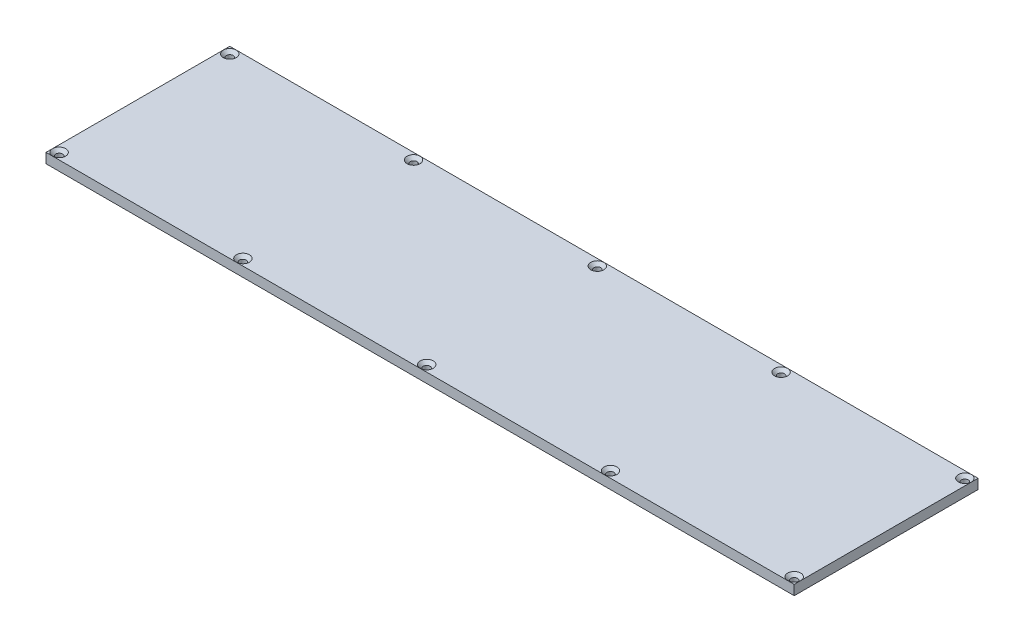
SolidWorks part; units mm, degrees
material "Wood floor laminate, Egger MED"
ref_plane "Front Plane" through (0, 0, 0) normal (0, 0, 1) x (1, 0, 0)
ref_plane "Top Plane" through (0, 0, 0) normal (0, 1, 0) x (1, 0, 0)
ref_plane "Right Plane" through (0, 0, 0) normal (1, 0, 0) x (0, 0, -1)
sketch "Sketch1" plane through (0, 0, 0) normal (0, 1, 0) x (1, 0, 0)
  line L1 (-361.95, -88.9) -> (361.95, -88.9)
  line L2 (-361.95, -88.9) -> (-361.95, 88.9)
  line L3 (-361.95, 88.9) -> (361.95, 88.9)
  line L4 (361.95, -88.9) -> (361.95, 88.9)
  line L5 (0, 88.9) -> (0, -88.9) construction
  line L6 (-361.95, 0) -> (361.95, 0) construction
  point P0 (0, 0)
  dimension "D1" = 723.9
  dimension "D2" = 177.8
extrude "Boss-Extrude1" add sketch "Sketch1" along normal blind 9.525
sketch "Sketch2" plane through (0, 9.525, 0) normal (0, 1, 0) x (1, 0, 0)
  line L0 (-361.95, -88.9) -> (361.95, -88.9) construction
  line L1 (-361.95, -88.9) -> (361.95, -88.9) construction
  line L2 (-361.95, -88.9) -> (-361.95, 88.9) construction
  line L3 (-361.95, 88.9) -> (361.95, 88.9) construction
  line L4 (361.95, -88.9) -> (361.95, 88.9) construction
  line L5 (0, 88.9) -> (0, -88.9) construction
  line L6 (-361.95, 0) -> (361.95, 0) construction
  line L7 (361.95, -88.9) -> (361.95, 88.9) construction
  line L8 (361.95, 88.9) -> (-361.95, 88.9) construction
  line L9 (-361.95, 88.9) -> (-361.95, -88.9) construction
  line L10 (-355.6, 82.55) -> (355.6, 82.55) construction
  line L11 (355.6, -82.55) -> (355.6, 82.55) construction
  line L12 (-355.6, -82.55) -> (355.6, -82.55) construction
  line L13 (-355.6, -82.55) -> (-355.6, 82.55) construction
  point P12 (-355.6, 82.55)
  point P13 (355.6, 82.55)
  point P14 (355.6, -82.55)
  point P15 (-355.6, -82.55)
  point P16 (-177.8, 82.55)
  point P17 (177.8, 82.55)
  point P19 (-177.8, -82.55)
  point P20 (177.8, -82.55)
  point P201 (355.6, -82.55)
  point P203 (-355.6, 82.55)
  point P205 (-355.6, -82.55)
  point P207 (0, -82.55)
  point P209 (0, 82.55)
  point P211 (355.6, 82.55)
  dimension "D2" = 177.8
  dimension "D3" = 177.8
  dimension "D1" = 6.35
hole_wizard "CSK for M6 Flat Head Machine Screw1" positions "Sketch2" profile "Sketch3" countersink size "M6" standard "ANSI Metric" end condition through all
sketch "Sketch3" plane through (355.6, 9.525, -82.55) normal (1, 0, 0) x (0, 0, 1)
  line L0 (0, 0) -> (0, 9.525)
  line L1 (0, 9.525) -> (3.3, 9.525)
  line L2 (3.3, 9.525) -> (3.3, 3)
  line L3 (3.3, 3) -> (6.3, 0)
  line L5 (6.3, 0) -> (0, 0)
  line L6 (-3.3, 3) -> (-6.3, 0) construction
  line L11 (0, -6.35) -> (0, 107.95) construction
  dimension "Thru Hole Dia." = 6.6
  dimension "Thru Hole Depth" = 9.525
  dimension "Near C'Sink Dia." = 12.6
  dimension "Near C'Sink Angle" = 90
equation "\"D3@Sketch2\"=\"D2@Sketch2\""
